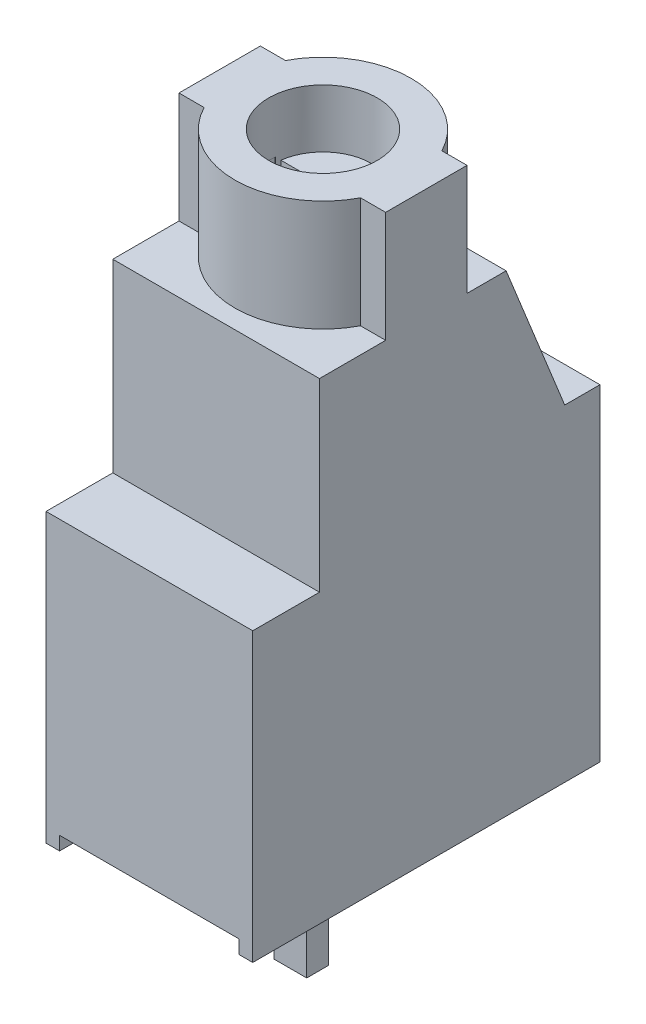
SolidWorks part; units mm, degrees
ref_plane "前视基准面" through (0, 0, 0) normal (0, 0, 1) x (1, 0, 0)
ref_plane "上视基准面" through (0, 0, 0) normal (0, 1, 0) x (1, 0, 0)
ref_plane "右视基准面" through (0, 0, 0) normal (1, 0, 0) x (0, 0, -1)
sketch "草图2" plane through (0, 0, 0) normal (1, 0, 0) x (0, 0, -1)
  line L0 (6.4, 0) -> (-6.4, 0)
  line L1 (-6.4, 0) -> (-6.4, 10.5915)
  line L2 (-6.4, 10.5915) -> (-3.9397, 10.5915)
  line L3 (-3.9397, 10.5915) -> (-3.9397, 17.413)
  line L4 (-3.9397, 17.413) -> (-1.5, 17.413)
  line L5 (-1.5, 17.413) -> (-1.5, 21.5)
  line L6 (-1.5, 21.5) -> (1.5, 21.5)
  line L7 (1.5, 21.5) -> (1.5, 17.413)
  line L8 (5.102, 12.0465) -> (2.94, 17.413)
  line L9 (5.102, 12.0465) -> (6.4, 12.0465)
  line L10 (6.4, 12.0465) -> (6.4, 0)
  line L11 (0, 82.2465) -> (0, -29.6489) construction
  line L12 (2.94, 17.413) -> (1.5, 17.413)
  dimension "D1" = 12.8
  dimension "D2" = 21.5
  dimension "D3" = 3
extrude "凸台-拉伸1" add sketch "草图2" along normal blind 3.81 and the other way blind 3.81
sketch "草图3" plane through (0, 21.5, 0) normal (0, 1, 0) x (1, 0, 0)
  circle A0 centre (0, 0) radius 3.25
  dimension "D1" = 6.5
extrude "凸台-拉伸2" add sketch "草图3" against normal up to next (21.5 mm away)
sketch "草图4" plane through (0, 21.5, 0) normal (0, 1, 0) x (1, 0, 0)
  circle A0 centre (0, 0) radius 2
  dimension "D1" = 4
extrude "切除-拉伸1" cut sketch "草图4" against normal blind 2
sketch "草图7" plane through (0, 19.5, 0) normal (0, 1, 0) x (1, 0, 0)
  circle A1 centre (0, 0) radius 2 construction
  circle A2 centre (0, 0) radius 2
  circle A3 centre (0, 0) radius 1.8
  dimension "D1" = 0.2
extrude "切除-拉伸5" cut sketch "草图7" against normal blind 0.5
sketch "草图5" plane through (0, 19.5, 0) normal (0, 1, 0) x (1, 0, 0)
  line L0 (2.9198, 0) -> (-3.0795, 0) construction
  line L1 (-2, 0.232) -> (2, 0.232)
  line L2 (-2, 0.232) -> (-2, -0.232)
  line L3 (-2, -0.232) -> (2, -0.232)
  line L4 (2, 0.232) -> (2, -0.232)
  line L5 (0, 1.1079) -> (0, -1.2643) construction
  circle A0 centre (0, 0) radius 2 construction
extrude "切除-拉伸2" cut sketch "草图5" against normal blind 0.5
sketch "草图8" plane through (0, 0, -6.4) normal (0, 0, -1) x (-1, 0, 0)
  line L0 (0, -8.4917) -> (0, 27.7719) construction
  line L2 (-1.9173, 7.8501) -> (1.9173, 7.8501)
  line L3 (-1.9173, 7.8501) -> (-1.9173, 4.0836)
  line L4 (-1.9173, 4.0836) -> (1.9173, 4.0836)
  line L5 (1.9173, 7.8501) -> (1.9173, 4.0836)
extrude "切除-拉伸6" cut sketch "草图8" against normal blind 2
chamfer "倒角1" distance 1 angle 60 4 edges at (0, 7.8501, -6.4) (-1.9173, 5.9668, -6.4) (1.9173, 5.9668, -6.4) (0, 4.0836, -6.4) first distance on face at (0, 5.9668, -6.4)
sketch "草图9" plane through (0, 0, 0) normal (0, -1, 0) x (1, 0, 0)
  line L0 (-3.81, 6.4) -> (3.81, 6.4) construction
  line L1 (-3.31, 6.4) -> (3.31, 6.4)
  line L2 (-3.31, 6.4) -> (-3.31, -6.4)
  line L3 (-3.31, -6.4) -> (3.31, -6.4)
  line L4 (3.31, 6.4) -> (3.31, -6.4)
  line L5 (-3.81, -6.4) -> (3.81, -6.4) construction
  line L6 (0, 11.6522) -> (0, -12.157) construction
  line L7 (-3.81, 6.4) -> (-3.81, -6.4) construction
  line L8 (3.81, 6.4) -> (3.81, -6.4) construction
  point P10 (-3.81, 0)
  dimension "D1" = 0.5
  dimension "D2" = 0.5
extrude "切除-拉伸7" cut sketch "草图9" against normal blind 0.5
sketch "草图10" plane through (0, 0.5, 0) normal (0, -1, 0) x (1, 0, 0)
  line L0 (0, 2.8369) -> (0, -1.126) construction
  line L1 (-0.6, 1.2) -> (0.6, 1.2)
  line L2 (-0.6, 1.2) -> (-0.6, 0.4)
  line L3 (-0.6, 0.4) -> (0.6, 0.4)
  line L4 (0.6, 1.2) -> (0.6, 0.4)
  line L5 (-1.1133, 0.8) -> (0.9224, 0.8) construction
  line L6 (3.31, 6.4) -> (-3.31, 6.4) construction
  dimension "D1" = 1.2
  dimension "D2" = 0.8
  dimension "D3" = 5.6
extrude "凸台-拉伸4" add sketch "草图10" along normal blind 5.2
